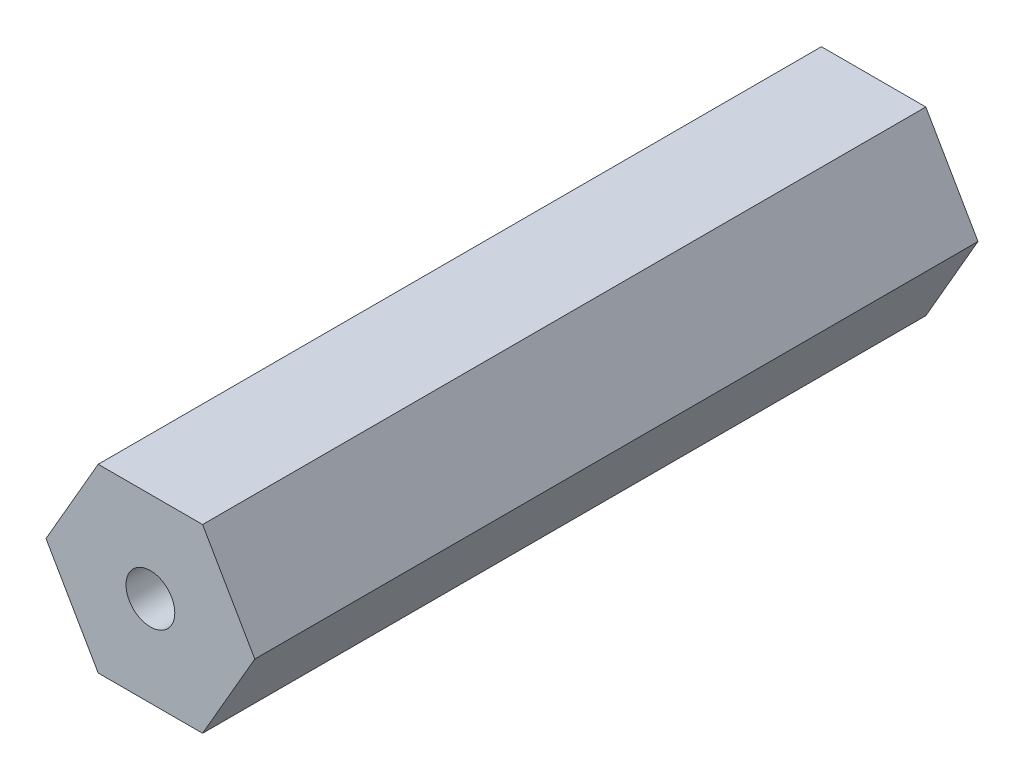
SolidWorks part; units mm, degrees
material "7075-T6 (SN)"
ref_plane "Front Plane" through (0, 0, 0) normal (0, 0, 1) x (1, 0, 0)
ref_plane "Top Plane" through (0, 0, 0) normal (0, 1, 0) x (1, 0, 0)
ref_plane "Right Plane" through (0, 0, 0) normal (1, 0, 0) x (0, 0, -1)
other "Configuration Table"
sketch "Sketch1" plane through (0, 0, 0) normal (0, 0, 1) x (1, 0, 0)
  line L1 (7.3323, 0) -> (3.6662, 6.35)
  line L2 (3.6662, 6.35) -> (-3.6662, 6.35)
  line L3 (-3.6662, 6.35) -> (-7.3323, 0)
  line L4 (-7.3323, 0) -> (-3.6662, -6.35)
  line L5 (-3.6662, -6.35) -> (3.6662, -6.35)
  line L6 (3.6662, -6.35) -> (7.3323, 0)
  circle A0 centre (0, 0) radius 6.35 construction
  circle A1 centre (0, 0) radius 1.7145
  dimension "D2" = 3.429
  dimension "D1" = 12.7
extrude "Boss-Extrude1" add sketch "Sketch1" along normal mid plane 50.8
fillet "Fillet1" [suppressed] radius 0.635
equation "\"length\"= 2"
equation "\"D1@Boss-Extrude1\"=\"length\""
